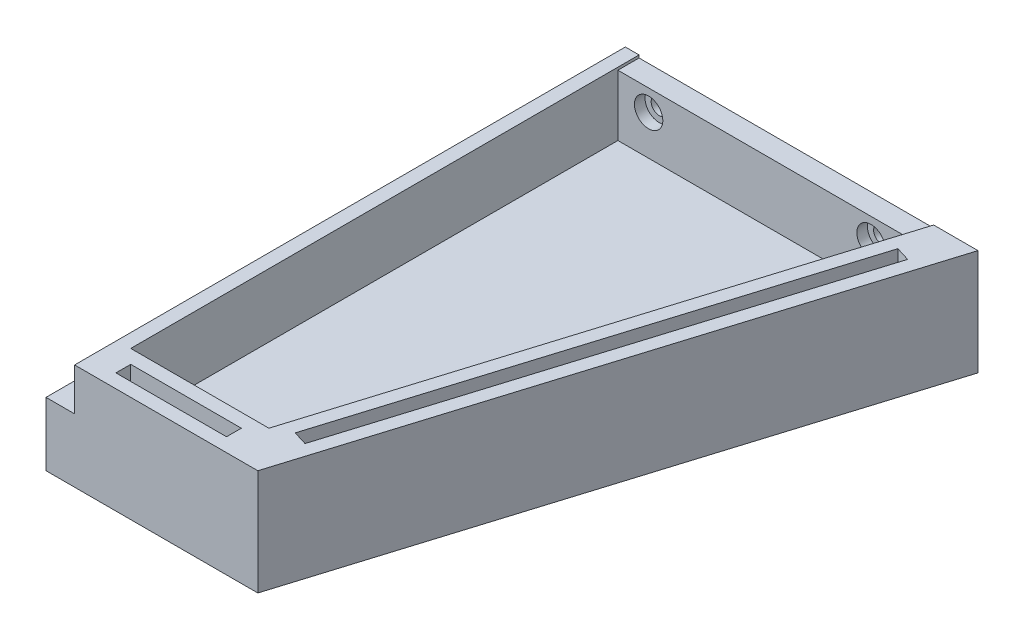
SolidWorks part; units mm, degrees
ref_plane "Front Plane" through (0, 0, 0) normal (1, 0, 0) x (0, 1, 0)
ref_plane "Top Plane" through (0, 0, 0) normal (0, 0, 1) x (0, 1, 0)
ref_plane "Right Plane" through (0, 0, 0) normal (0, 1, 0) x (-1, 0, 0)
sketch "Sketch1" plane through (0, 0, 0) normal (0, 1, 0) x (-1, 0, 0)
  line L0 (-13.4363, 17.5951) -> (26.5637, 147.5951)
  line L1 (-13.4363, 10.0951) -> (-8.4363, 10.0951)
  line L2 (-13.4363, 10.0951) -> (-13.4363, 17.5951)
  line L3 (-13.4363, 17.5951) -> (-8.4363, 17.5951)
  line L4 (-8.4363, 10.0951) -> (-8.4363, 17.5951)
  line L13 (-13.4363, 17.5951) -> (26.5637, 147.5951)
  line L14 (-13.4363, 17.5951) -> (-3.8786, 14.6542)
  line L15 (-13.4363, 17.5951) -> (66.5637, 17.5951) construction
  line L16 (-13.4363, 17.5951) -> (-13.4363, 137.5951) construction
  line L17 (-13.4363, 137.5951) -> (66.5637, 137.5951) construction
  line L18 (66.5637, 17.5951) -> (66.5637, 137.5951) construction
  line L19 (66.5637, 137.5951) -> (26.5637, 137.5951)
  line L20 (66.5637, 137.5951) -> (66.5637, 147.5951)
  line L21 (66.5637, 147.5951) -> (26.5637, 147.5951)
  line L22 (26.5637, 137.5951) -> (26.5637, 147.5951)
  line L23 (26.5637, 147.5951) -> (36.1214, 144.6542)
  line L24 (-3.8786, 14.6542) -> (36.1214, 144.6542)
  line L25 (-8.4363, 17.5951) -> (-2.9737, 17.5951)
  line L27 (-2.9737, 17.5951) -> (66.5637, 17.5951)
  line L28 (-2.9737, 17.5951) -> (-2.9737, 22.5951)
  line L29 (-2.9737, 22.5951) -> (66.5637, 22.5951)
  line L30 (66.5637, 17.5951) -> (66.5637, 22.5951)
  line L35 (66.5637, 147.5951) -> (76.5637, 147.5951)
  line L36 (66.5637, 147.5951) -> (66.5637, 17.5951)
  line L37 (66.5637, 17.5951) -> (76.5637, 17.5951)
  line L38 (76.5637, 147.5951) -> (76.5637, 17.5951)
  point P17 (66.5637, 17.5951)
  dimension "D1" = 7.5
  dimension "D2" = 5
  dimension "D3" = 120
  dimension "D4" = 80
  dimension "D5" = 10
  dimension "D6" = 40
  dimension "D7" = 10
  dimension "D9" = 5
  dimension "D8" = 10
extrude "Boss-Extrude1" add sketch "Sketch1" along normal blind 25 contours L24 L19 L20 L21 L23 | L19 L24 L23 L22 | L28 L29 L24 L19 L22 L0 L3 L25 | L38 L35 L20 L36 L30 L37 | L29 L28 L24 | L27 L30 L29 L24 region at (-10.4807, 0, 78.5361) region at (-30.6185, 0, 142.1049) region at (-50.1746, 0, 142.7061) region at (-71.5637, 0, 82.5951) region at (2.4609, 0, 20.9284) region at (-32.1782, 0, 20.0858)
sketch "Sketch3" plane through (0, 0, 0) normal (0, -1, 0) x (1, 0, 0)
  line L0 (-76.5637, 147.5951) -> (-26.5637, 147.5951)
  line L1 (-26.5637, 147.5951) -> (13.4363, 17.5951)
  line L2 (13.4363, 17.5951) -> (-76.5637, 17.5951)
  line L3 (-76.5637, 17.5951) -> (-76.5637, 147.5951)
extrude "Boss-Extrude2" add sketch "Sketch3" against normal blind 10
sketch "Sketch4" plane through (0, 25, 0) normal (0, 1, 0) x (-1, 0, 0)
  line L0 (33.9494, 137.5951) -> (-1.4352, 22.5951)
  line L1 (33.9494, 137.5951) -> (66.5637, 137.5951)
  line L2 (33.9494, 137.5951) -> (33.9494, 147.5951)
  line L3 (33.9494, 147.5951) -> (66.5637, 147.5951)
  line L4 (66.5637, 137.5951) -> (66.5637, 147.5951)
  line L5 (33.9494, 137.5951) -> (24.3916, 140.5359)
  line L6 (-1.4352, 22.5951) -> (-10.993, 25.5359)
  line L7 (24.3916, 140.5359) -> (-10.993, 25.5359)
  line L9 (29.8873, 135.4446) -> (-3.5857, 26.6571)
  line L10 (-3.5857, 26.6571) -> (-6.9309, 27.6864)
  line L11 (26.5421, 136.4739) -> (-6.9309, 27.6864)
  line L12 (29.8873, 135.4446) -> (26.5421, 136.4739)
  line L13 (37.1994, 140.8451) -> (37.1994, 144.3451)
  line L14 (37.1994, 144.3451) -> (63.3137, 144.3451)
  line L15 (63.3137, 140.8451) -> (63.3137, 144.3451)
  line L16 (37.1994, 140.8451) -> (63.3137, 140.8451)
  line L17 (76.5637, 147.5951) -> (26.5637, 147.5951) construction
  line L18 (26.5421, 136.4739) -> (29.964, 147.5951)
  line L20 (29.8873, 135.4446) -> (33.626, 147.5951)
  line L21 (33.626, 147.5951) -> (29.964, 147.5951)
  line L22 (37.1994, 144.3451) -> (28.964, 144.3451)
  line L23 (28.964, 144.3451) -> (27.8871, 140.8451)
  line L24 (27.8871, 140.8451) -> (37.1994, 140.8451)
  line L25 (-13.4363, 17.5951) -> (26.5637, 147.5951) construction
  point P4 (67.1771, 147.5951)
  point P12 (66.5637, 137.5951)
  point P24 (33.9494, 137.5951)
  point P25 (24.4867, 140.8451)
  point P30 (-1.4352, 22.5951)
  dimension "D1" = 3.25
extrude "Cut-Extrude1" cut sketch "Sketch4" against normal blind 10 contours L9 L12 L11 L10 | L13 L16 L15 L14 region at (-50.2565, 25, 142.5951) region at (-11.4782, 25, 81.5655)
sketch "Sketch5" plane through (0, 25, -3.0299) normal (0, -1, 0) x (1, 0, 0)
  line L5 (13.4363, 20.625) -> (-76.5637, 20.625) construction
  line L6 (-66.5637, 25.625) -> (1.4352, 25.625)
  line L7 (-66.5637, 25.625) -> (-66.5637, 20.625)
  line L8 (-66.5637, 20.625) -> (1.4352, 20.625)
  line L9 (1.4352, 25.625) -> (1.4352, 20.625)
  line L10 (1.4352, 25.625) -> (2.9737, 20.625)
  line L11 (1.4352, 25.625) -> (-33.9494, 140.625) construction
  line L12 (2.9737, 20.625) -> (1.4352, 20.625)
  line M9 (-66.5637, 25.625) -> (1.4352, 25.625)
  line M14 (13.4363, 20.625) -> (-76.5637, 20.625)
extrude "Cut-Extrude2" cut sketch "Sketch5" along normal blind 0.625 contours L9 L10 M14 | L9 L7 M9 M14 region at (-32.5642, 25, 20.0951) region at (1.948, 25, 19.2617)
sketch "Sketch6" plane through (0, 0, 22.5951) normal (0, 0, 1) x (1, 0, 0)
  line L1 (-66.5637, 24.375) -> (-59.3137, 24.375) construction
  line L2 (-66.5637, 24.375) -> (-66.5637, 19.375) construction
  line L3 (-66.5637, 19.375) -> (-59.3137, 19.375) construction
  line L4 (-59.3137, 24.375) -> (-59.3137, 19.375) construction
  circle A0 centre (-59.3137, 19.375) radius 1.9
  point P6 (-66.5637, 25)
  dimension "D2" = 5
  dimension "D3" = 3.8
  dimension "D1" = 7.25
extrude "Cut-Extrude3" cut sketch "Sketch6" against normal up to next
sketch "Sketch7" plane through (0, 0, 22.5951) normal (0, 0, 1) x (1, 0, 0)
  circle A0 centre (-59.3137, 19.375) radius 3.35
  dimension "D1" = 6.7
extrude "Cut-Extrude4" cut sketch "Sketch7" against normal blind 2.5
pattern_linear "LPattern1" count 2 spacing 52.5 along (1, 0, 0) of "Cut-Extrude4", "Cut-Extrude3"
sketch "Sketch8" plane through (0, 25, 0) normal (0, 1, 0) x (-1, 0, 0)
  line L0 (76.5637, 147.5951) -> (26.5637, 147.5951) construction
  line L1 (66.5637, 17.5951) -> (69.8137, 17.5951)
  line L2 (66.5637, 17.5951) -> (66.5637, 147.5951)
  line L3 (66.5637, 147.5951) -> (69.8137, 147.5951)
  line L4 (69.8137, 17.5951) -> (69.8137, 147.5951)
  line L5 (66.5637, 17.5951) -> (76.5637, 17.5951) construction
  line L6 (76.5637, 147.5951) -> (73.3137, 147.5951)
  line L7 (76.5637, 147.5951) -> (76.5637, 17.5951)
  line L8 (76.5637, 17.5951) -> (73.3137, 17.5951)
  line L9 (73.3137, 147.5951) -> (73.3137, 17.5951)
  line L11 (73.3137, 17.5951) -> (69.8137, 17.5951)
  line L12 (73.3137, 17.5951) -> (73.3137, 147.5951)
  line L13 (73.3137, 147.5951) -> (69.8137, 147.5951)
  line L14 (69.8137, 17.5951) -> (69.8137, 147.5951)
  line M8 (66.5637, 17.5951) -> (76.5637, 17.5951)
  line M9 (76.5637, 17.5951) -> (76.5637, 147.5951)
  line M10 (76.5637, 147.5951) -> (26.5637, 147.5951)
  dimension "D1" = 3.25
  dimension "D2" = 3.25
extrude "Cut-Extrude5" cut sketch "Sketch8" against normal blind 10 contours L9 L4 M10 M8 | L9 M10 M8 M9 region at (-71.5637, 25, 82.5951) region at (-74.9387, 25, 82.5951)
equation "\"whitekey_cutout_length\"= 101.5"
equation "\"whitekey_spacing\"=1.25"
equation "\"key_mount_recess_length\"=50"
equation "\"key_mount_recess_height\"=12.5"
equation "\"key_mount_recess_depth\"=1.5"
equation "\"wall_thickness\"=10"
equation "\"guide_brace_height\"=20"
equation "\"guide_brace_thickness\"=2"
equation "\"dowel_recess_depth\"=10"
equation "\"dowel_recess_offset\"=3.25"
equation "\"dowel_insert_tolerance\"=0.1"
equation "\"base_mount_height\"=40"
equation "\"base_rear_length\"=80"
equation "\"base_front_length\"=111.5"
equation "\"screw_hole_wall_offset\"=7.25"
equation "\"screw_hole_edge_inset\"=\"dowel_recess_depth\"/2"
equation "\"screw_hole_diameter\"=3.8"
equation "\"screw_head_hole_diameter\"=6.7"
equation "\"screw_nut_hole_side_len\"=3.5"
equation "\"screw_nut_recess_offset\"=0.35"
equation "\"screw_head_and_nut_recess_depth\"=2.5"
equation "\"screw_shaft_diameter\"=3.5"
equation "\"switch_board_width\"=30"
equation "\"switch_board_thickness\"=1.6"
equation "\"switch_board_wall_offset\"=11.5"
equation "\"heatset_insert_hole_diameter\"=4.8"
equation "\"heatset_insert_hole_depth\"=3.8"
equation "\"front_rear_panel_width\"=23.75"
equation "\"front_panel_height\"=24"
equation "\"front_rear_panel_recess_depth\"=5"
equation "\"rod_diameter\"=5"
equation "\"rod_head_diameter\"=8"
equation "\"rod_length_adj\"=0.5"
equation "\"rod_insert_length\"=2.8"
equation "\"switch_black_key_mount_height\"=8"
equation "\"switch_white_key_mount_height\"=3"
equation "\"side_panel_depth\"=25"
equation "\"D5@Sketch1\"=\"wall_thickness\""
equation "\"D7@Sketch1\"=\"wall_thickness\""
equation "\"D8@Sketch1\"=\"wall_thickness\""
equation "\"D9@Sketch1\"=\"wall_thickness\"/2"
equation "\"D2@Sketch1\"=\"wall_thickness\"/2"
equation "\"D1@Sketch1\"=\"wall_thickness\"*0.75"
equation "\"D3@Sketch1\"=\"base_mount_height\"*3"
equation "\"D4@Sketch1\"=\"base_rear_length\""
equation "\"D1@Boss-Extrude1\"=\"side_panel_depth\""
equation "\"D1@Boss-Extrude2\"=\"wall_thickness\""
equation "\"D1@Sketch4\"=\"dowel_recess_offset\""
equation "\"D1@Cut-Extrude1\"=\"dowel_recess_depth\""
equation "\"D1@Sketch6\"=\"screw_hole_wall_offset\""
equation "\"D2@Sketch6\"=\"screw_hole_edge_inset\""
equation "\"D3@Sketch6\"=\"screw_hole_diameter\""
equation "\"D1@Sketch7\"=\"screw_head_hole_diameter\""
equation "\"D3@LPattern1\"=\"base_rear_length\"-\"wall_thickness\"-\"screw_hole_wall_offset\"*2-3"
equation "\"D1@Sketch8\"=\"dowel_recess_offset\""
equation "\"D2@Sketch8\"=\"dowel_recess_offset\""
equation "\"D1@Cut-Extrude5\"=\"front_rear_panel_recess_depth\"*2"
equation "\"D1@Cut-Extrude2\"=\"whitekey_spacing\"/2"
